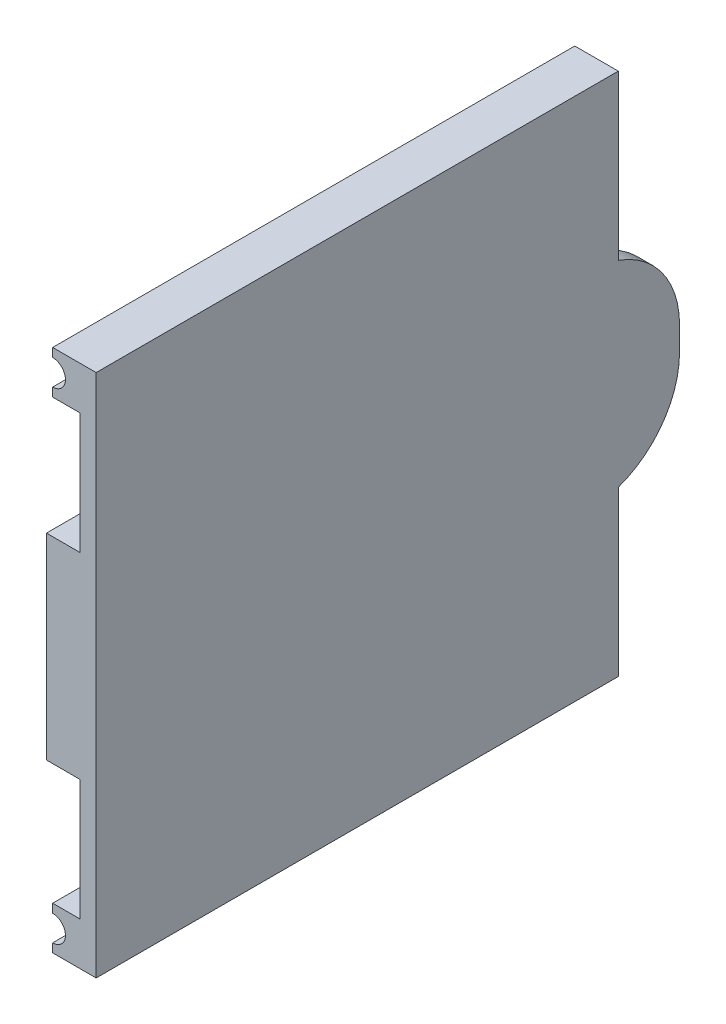
SolidWorks part; units mm, degrees
ref_plane "Alzado" through (0, 0, 0) normal (0, 0, 1) x (1, 0, 0)
ref_plane "Planta" through (0, 0, 0) normal (0, 1, 0) x (1, 0, 0)
ref_plane "Vista lateral" through (0, 0, 0) normal (1, 0, 0) x (0, 0, -1)
sketch "Croquis1" plane through (0, 0, 0) normal (0, 0, 1) x (1, 0, 0)
  line L0 (-9.35, 13.75) -> (-9.35, 36.65) construction
  line L5 (-13.6, 13.75) -> (-5.1, 13.75) construction
  line L6 (-13.6, 36.65) -> (-5.1, 36.65) construction
  line L7 (-9.35, 25.2) -> (-7.0041, 25.2) construction
  line L8 (-3.3192, -3.4208) -> (-1.5763, -3.4208)
  line L9 (-7.0041, 14.4717) -> (-5.3326, 14.4717)
  line L12 (-5.3326, 25.2) -> (-3.3192, 25.2) construction
  line L14 (-7.0041, 14.4717) -> (-7.0041, 35.9283)
  line L15 (-7.0041, 35.9283) -> (-5.3326, 35.9283)
  line L16 (-5.3326, 14.4717) -> (-5.3326, 35.9283)
  line L18 (-3.3192, -3.4208) -> (-3.3192, 53.8208)
  line L19 (-3.3192, 53.8208) -> (-1.5763, 53.8208)
  line L20 (-1.5763, -3.4208) -> (-1.5763, 53.8208)
  line L21 (-1.5763, 25.2) -> (1.1768, 25.2) construction
extrude "Saliente-Extruir1" add sketch "Croquis1" against normal up to surface (55 mm away)
sketch "Croquis2" plane through (0, 0, 0) normal (0, 0, 1) x (1, 0, 0)
  line L0 (-3.3192, 35.9283) -> (-3.3192, 53.8208)
  line L1 (-1.5763, -3.4208) -> (-3.3192, -3.4208)
  line L2 (-1.5763, -3.4208) -> (-1.5763, 53.8208)
  line L3 (-1.5763, 53.8208) -> (-3.3192, 53.8208)
  line L4 (-3.3192, -3.4208) -> (-3.3192, 14.4717)
  line L5 (-7.0041, 14.4717) -> (-3.3192, 14.4717)
  line L6 (-7.0041, 14.4717) -> (-7.0041, 35.9283)
  line L7 (-7.0041, 35.9283) -> (-3.3192, 35.9283)
  line L8 (-1.5763, 14.4717) -> (-1.5763, 35.9283)
  line M1 (-1.5763, -3.4208) -> (-1.5763, 53.8208)
  line M2 (-1.5763, 53.8208) -> (-3.3192, 53.8208)
  line M3 (-3.3192, 53.8208) -> (-3.3192, -3.4208)
  line M4 (-3.3192, -3.4208) -> (-1.5763, -3.4208)
extrude "Saliente-Extruir2" add sketch "Croquis2" along normal blind 2 contours L7 L6 L5 M3 | L2 M4 M1 M2 M3 region at (-5.1617, 25.2, 0) region at (-2.4477, 25.2, 0)
sketch "Croquis3" plane through (-3.3192, 0, 0) normal (-1, 0, 0) x (0, 0, 1)
  line L0 (-55, 25.2) -> (-84.072, 25.2) construction
  line L1 (-55, 35.9283) -> (-55, 14.4717) construction
  line L2 (-55, 14.4717) -> (-55, 35.9283) construction
  line L3 (-55, 53.8208) -> (-55, -3.4208) construction
  line L5 (-55, 14.4717) -> (-61.6895, 14.4717)
  line L6 (-55, 14.4717) -> (-55, 35.9283)
  line L7 (-55, 35.9283) -> (-61.6895, 35.9283)
  line L8 (-61.6895, 14.4717) -> (-61.6895, 35.9283)
extrude "Saliente-Extruir3" add sketch "Croquis3" against normal through all
fillet "Redondeo1" radius 10 2 edges at (-2.4477, 14.4717, -61.6895) (-2.4477, 35.9283, -61.6895)
ref_plane "Plano2" through (-4.3192, 0, 0) normal (-1, 0, 0) x (0, 0, 1)
sketch "Croquis6" plane through (-4.3192, 0, 0) normal (-1, 0, 0) x (0, 0, 1)
  line L0 (-58.022, 30.9962) -> (-58.022, 19.291)
  line L3 (-58.022, 19.291) -> (-58.022, 30.9962) construction
  ellipse E0 centre (-58.022, 25.1436) end of major axis (-58.022, 19.291) minor radius 2.2658 (-58.022, 30.9962) -> (-58.022, 19.291) ccw
  point P9 (-58.022, 25.1436)
revolve "Cortar-Revolución4" cut sketch "Croquis6" angle 360 about L3
sketch "Croquis7" plane through (0, 0, -55) normal (0, 0, -1) x (-1, 0, 0)
  line L0 (3.3192, 25.2) -> (14.6583, 25.2) construction
  line L1 (3.3192, 26.4922) -> (3.3192, 23.9078) construction
  line L2 (6.3251, 50.0746) -> (6.3251, 49.1229)
  line L3 (3.3192, 53.8208) -> (6.3251, 53.8208)
  line L4 (3.3192, 53.8208) -> (3.3192, 49.1229)
  line L5 (3.3192, 49.1229) -> (6.3251, 49.1229)
  line L6 (6.3251, 53.8208) -> (6.3251, 52.8692)
  line L7 (6.3251, -3.4208) -> (6.3251, -2.4692)
  line L8 (3.3192, -3.4208) -> (6.3251, -3.4208)
  line L9 (3.3192, -3.4208) -> (3.3192, 1.2771)
  line L10 (3.3192, 1.2771) -> (6.3251, 1.2771)
  line L11 (6.3251, 0.3254) -> (6.3251, 1.2771)
  arc A0 (6.3251, 52.8692) -> (6.3251, 50.0746) centre (6.3251, 51.4719) ccw
  arc A1 (6.3251, -2.4692) -> (6.3251, 0.3254) centre (6.3251, -1.0719) cw
extrude "Saliente-Extruir4" add sketch "Croquis7" against normal up to surface (57 mm away) up to face at (-3.8047, 25.2, 2)
